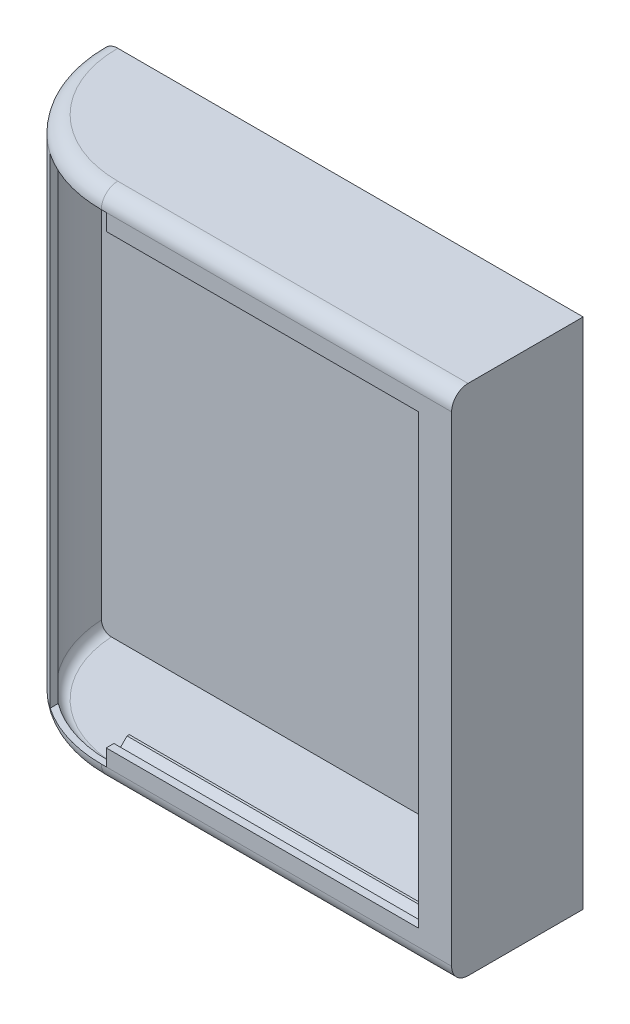
SolidWorks part; units mm, degrees
ref_plane "Front Plane" through (0, 0, 0) normal (0, 0, 1) x (1, 0, 0)
ref_plane "Top Plane" through (0, 0, 0) normal (0, 1, 0) x (1, 0, 0)
ref_plane "Right Plane" through (0, 0, 0) normal (1, 0, 0) x (0, 0, -1)
sketch "Sketch1" plane through (0, 0, 0) normal (0, 0, 1) x (1, 0, 0)
  line L0 (45.3286, -2) -> (120.3286, -2) construction
  line L1 (-101.1813, -2) -> (120.3286, -2) construction
  line L3 (45.3286, -2) -> (-101.1813, -2)
  line L4 (45.3286, -2) -> (45.3286, -158)
  line L5 (45.3286, -158) -> (-101.1813, -158)
  line L6 (-101.1813, -2) -> (-101.1813, -158)
extrude "Boss-Extrude1" add sketch "Sketch1" along normal blind 40
fillet "Fillet3" radius 40 1 edges at (-101.1813, -80, 40)
fillet "Fillet4" radius 5 4 edges at (-89.4655, -158, 28.2843) (-89.4655, -2, 28.2843) (-7.9263, -158, 40) (-7.9263, -2, 40)
shell "Shell4" thickness 2 removed face at (45.3286, -80, 25.3452)
sketch "Sketch19" plane through (0, 0, 40) normal (0, 0, 1) x (1, 0, 0)
  line L1 (-83.6714, -153) -> (45.3286, -153)
  line L2 (-83.6714, -153) -> (-83.6714, -7)
  line L3 (-83.6714, -7) -> (45.3286, -7)
  line L4 (45.3286, -153) -> (45.3286, -7)
  dimension "D1" = 129
extrude "Cut-Extrude8" cut sketch "Sketch19" against normal blind 10
sketch "Sketch21" plane through (0, -153, 0) normal (0, 1, 0) x (1, 0, 0)
  line L1 (45.3286, -40) -> (-59.6827, -40)
  line L2 (45.3286, -40) -> (45.3286, -38)
  line L3 (45.3286, -38) -> (-59.6827, -38)
  line L4 (-59.6827, -40) -> (-59.6827, -38)
  line L5 (-61.1813, -38) -> (45.3286, -38) construction
extrude "Boss-Extrude7" add sketch "Sketch21" along normal blind 5
sketch "Sketch22" plane through (45.3286, 0, 0) normal (1, 0, 0) x (0, 0, -1)
  line L0 (-38, -148) -> (-33, -148)
  line L1 (-33, -148) -> (-33, -156)
  line L2 (-35, -156) -> (-2, -156) construction
  line L3 (-33, -156) -> (-35, -156)
  line L4 (-38, -148) -> (-38, -153)
  line L5 (-38, -148) -> (-38, -153) construction
  arc A0 (-38, -153) -> (-35, -156) centre (-35, -153) ccw construction
  arc A1 (-35, -156) -> (-38, -153) centre (-35, -153) cw
  dimension "D1" = 5
extrude "Boss-Extrude8" add sketch "Sketch22" against normal up to surface (105.0113 mm away) up to face at (-59.6827, -150.5, 39)
sketch "Sketch23" plane through (45.3286, 0, 0) normal (1, 0, 0) x (0, 0, -1)
  line L4 (-37.6679, -148) -> (-37.6679, -152.0471)
  line L5 (-40, -148) -> (-33, -148) construction
  line L6 (-37.6679, -152.0471) -> (-33.6841, -148)
  line L7 (-33.6841, -148) -> (-37.6679, -148)
  point P5 (-37.6679, -152.0471)
  point P7 (-33, -148)
  point P9 (-33.9644, -148)
  point P10 (-33.6841, -148)
extrude "Cut-Extrude9" cut sketch "Sketch23" against normal up to surface (105.0113 mm away) up to face at (-59.6827, -152.4369, 36.6036)
sketch "Sketch24" plane through (0, -148, 0) normal (0, 1, 0) x (1, 0, 0)
  line L0 (-59.6827, -33) -> (-83.6036, -33) construction
ref_plane "Plane4" through (0, -80, 0) normal (0, 1, 0) x (1, 0, 0)
mirror "Mirror1" about plane through (0, -80, 0) normal (0, 1, 0) of "Boss-Extrude7", "Boss-Extrude8", "Cut-Extrude9"
sketch "Sketch25" plane through (45.3286, 0, 0) normal (1, 0, 0) x (0, 0, -1)
  line L0 (-40, -148) -> (-37.6679, -148)
  line L1 (-37.6679, -148) -> (-37.6679, -152.0471)
  line L2 (-37.6679, -152.0471) -> (-33.6841, -148)
  line L3 (-33.6841, -148) -> (-33, -148)
  line L4 (-33, -148) -> (-33, -156)
  line L5 (-33, -156) -> (-2, -156)
  line L6 (-2, -156) -> (-2, -4)
  line L7 (-2, -4) -> (-33, -4)
  line L8 (-33, -4) -> (-33, -12)
  line L9 (-33, -12) -> (-33.6841, -12)
  line L10 (-33.6841, -12) -> (-37.6679, -7.9529)
  line L11 (-37.6679, -7.9529) -> (-37.6679, -12)
  line L12 (-37.6679, -12) -> (-40, -12)
  line L13 (-40, -12) -> (-37.6679, -12) construction
  line L14 (-40, -12) -> (-40, -148)
extrude "Boss-Extrude9" add sketch "Sketch25" against normal blind 10
sketch "Sketch26" plane through (0, 0, 40) normal (0, 0, 1) x (1, 0, 0)
  line L0 (45.3286, -7) -> (43.3286, -7) construction
  line L1 (45.3286, -7) -> (-59.6827, -7) construction
  line L2 (35.3286, -148) -> (35.3286, -153) construction
  line L3 (-59.6827, -153) -> (45.3286, -153) construction
  line L4 (35.3286, -153) -> (37.3286, -153) construction
  line L6 (43.3286, -7) -> (37.3286, -7)
  line L7 (43.3286, -7) -> (43.3286, -153)
  line L8 (43.3286, -153) -> (37.3286, -153)
  line L9 (37.3286, -7) -> (37.3286, -153)
  dimension "D1" = 2
  dimension "D2" = 2
extrude "Cut-Extrude10" cut sketch "Sketch26" against normal blind 38
sketch "Sketch28" plane through (0, 0, 40) normal (0, 0, 1) x (1, 0, 0)
  line L1 (43.3286, -153) -> (37.3286, -153)
  line L2 (43.3286, -153) -> (43.3286, -7)
  line L3 (43.3286, -7) -> (37.3286, -7)
  line L4 (37.3286, -153) -> (37.3286, -7)
extrude "Boss-Extrude10" add sketch "Sketch28" against normal blind 2
